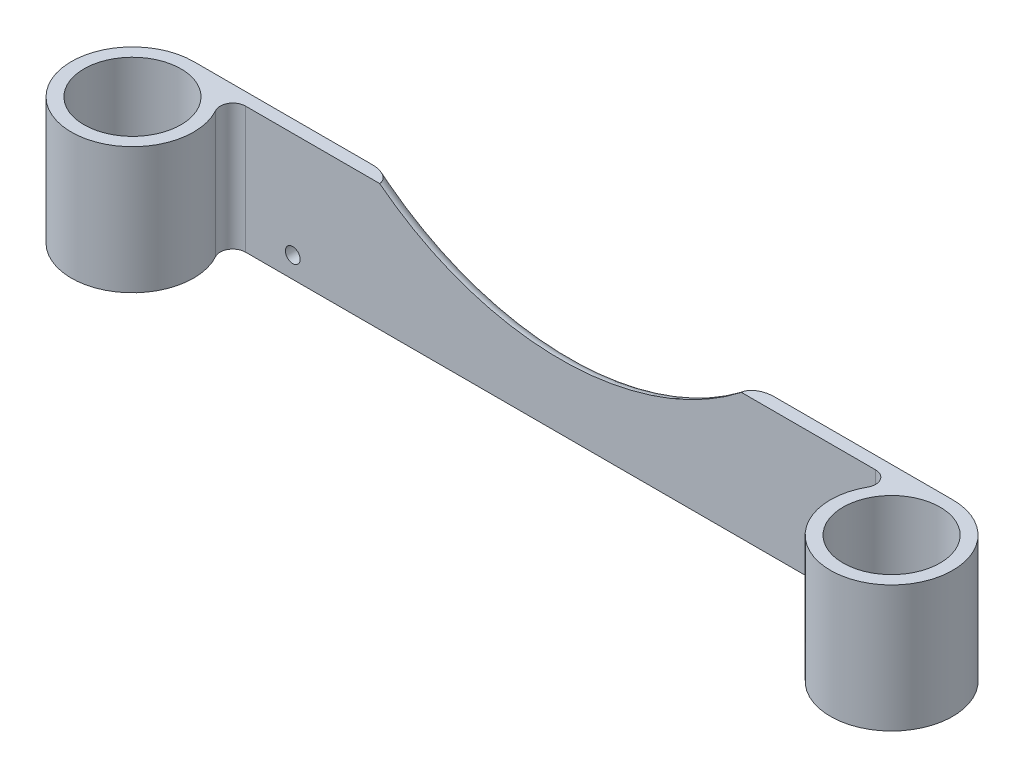
SolidWorks part; units mm, degrees
ref_plane "Front Plane" through (0, 0, 0) normal (0, 0, 1) x (1, 0, 0)
ref_plane "Top Plane" through (0, 0, 0) normal (0, 1, 0) x (1, 0, 0)
ref_plane "Right Plane" through (0, 0, 0) normal (1, 0, 0) x (0, 0, -1)
sketch "Sketch1" plane through (0, 0, 0) normal (0, 1, 0) x (1, 0, 0)
  line L0 (0, 14.5) -> (180, 14.5)
  line L1 (8.8318, 11.5) -> (171.1682, 11.5)
  arc A0 (0, 14.5) -> (8.8318, 11.5) centre (0, 0) ccw
  circle A1 centre (0, 0) radius 11.5
  circle A2 centre (180, 0) radius 11.5
  arc A3 (171.1682, 11.5) -> (180, 14.5) centre (180, 0) ccw
  dimension "D1" = 29
  dimension "D2" = 23
  dimension "D3" = 180
  dimension "D4" = 3
extrude "Boss-Extrude1" add sketch "Sketch1" along normal blind 30
fillet "Fillet1" radius 3 2 edges at (171.1682, 15, -11.5) (8.8318, 15, -11.5)
sketch "Sketch2" plane through (0, 0, -14.5) normal (0, 0, -1) x (-1, 0, 0)
  line L0 (-90, 0) -> (-90, 94.3813) construction
  line L1 (-180, 0) -> (0, 0) construction
  line L2 (-180, 30) -> (-180, 0) construction
  line L3 (0, 30) -> (0, 0) construction
  circle A0 centre (-90, 85.3132) radius 70
  circle A1 centre (-26.5, 5) radius 1.75
  circle A2 centre (-153.5, 5) radius 1.75
  point P14 (-90, 87.1249)
  point P15 (-90, 82.1285)
  point P16 (-28.606, 4.7201)
  point P17 (-90, 94.3813)
  point P18 (-90, 85.3132)
  dimension "D1" = 140
  dimension "D3" = 3.5
  dimension "D4" = 3.5
  dimension "D2" = 26.5
  dimension "D5" = 26.5
  dimension "D6" = 5
  dimension "D7" = 5
extrude "Cut-Extrude1" cut sketch "Sketch2" against normal blind 30
fillet "Fillet2" radius 3 1 edges at (90, 15.3132, -14.5)
